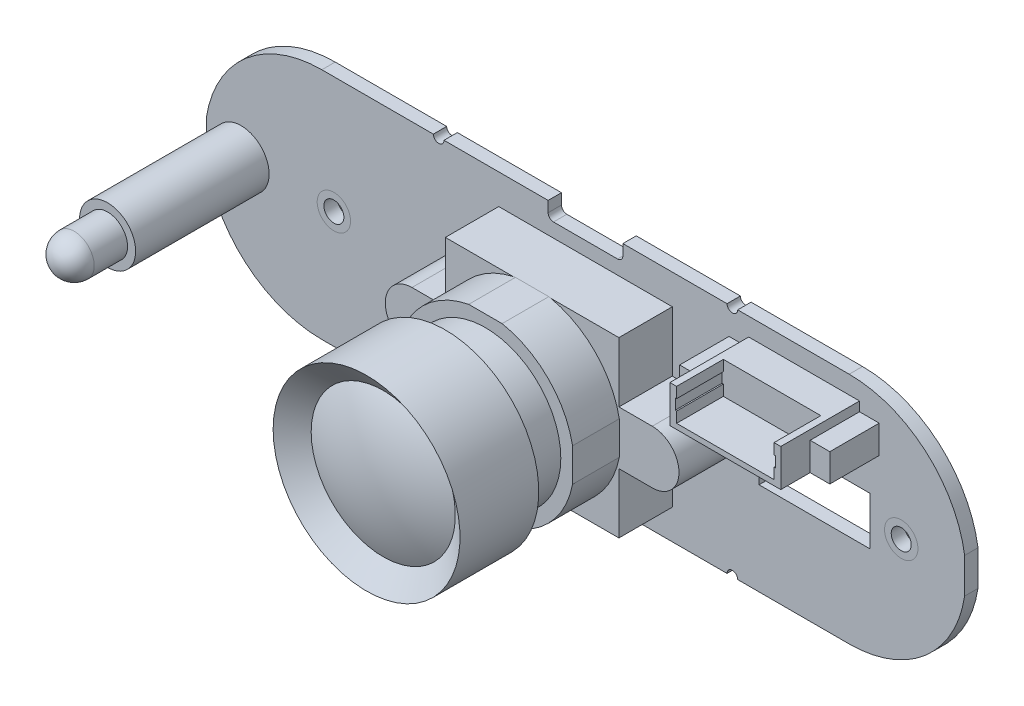
SolidWorks part; units mm, degrees
ref_plane "Front Plane" through (0, 0, 0) normal (0, 0, 1) x (1, 0, 0)
ref_plane "Top Plane" through (0, 0, 0) normal (0, 1, 0) x (1, 0, 0)
ref_plane "Right Plane" through (0, 0, 0) normal (1, 0, 0) x (0, 0, -1)
sketch "Sketch1" plane through (0, 0, 0) normal (0, 0, 1) x (1, 0, 0)
  line L0 (-19.75, 0) -> (19.75, 0) construction
  line L1 (-19.75, 8.75) -> (19.75, 8.75)
  line L2 (-19.75, -8.75) -> (19.75, -8.75)
  line L3 (28.4, 0) -> (-28.4, 0) construction
  line L4 (0, 8.75) -> (0, -8.75) construction
  arc A0 (-19.75, 8.75) -> (-19.75, -8.75) centre (-19.75, 0) ccw
  arc A1 (19.75, -8.75) -> (19.75, 8.75) centre (19.75, 0) ccw
  point P2 (0, 0)
  point P11 (0, 0)
  point P14 (0, 0)
  point P17 (28.4, 0)
  dimension "D1" = 8.75
  dimension "D2" = 39.5
  dimension "D3" = 56.8
extrude "Boss-Extrude1" add sketch "Sketch1" along normal mid plane 1
sketch "Sketch2" plane through (0, 0, 0) normal (0, 0, 1) x (1, 0, 0)
  line L0 (28.4, 0) -> (-28.4, 0) construction
  line L1 (28.4, 5) -> (28.4, -5)
  line L2 (-28.4, 5) -> (-28.4, -5)
  line L4 (28.4, 5) -> (30.4, 5)
  line L5 (30.4, 5) -> (30.4, -5)
  line L6 (30.4, -5) -> (28.4, -5)
  line L7 (-28.4, 5) -> (-30.4, 5)
  line L8 (-30.4, 5) -> (-30.4, -5)
  line L9 (-30.4, -5) -> (-28.4, -5)
  line L10 (19.75, 8.75) -> (-19.75, 8.75) construction
  line L11 (2.4, 7.55) -> (-2.4, 7.55)
  line L12 (2.8, 7.95) -> (2.8, 9.95)
  line L13 (2.8, 9.95) -> (-2.8, 9.95)
  line L14 (-2.8, 7.95) -> (-2.8, 9.95)
  line L15 (2.8, 7.55) -> (-2.8, 9.95) construction
  line L16 (2.8, 9.95) -> (-2.8, 7.55) construction
  arc A0 (2.4, 7.55) -> (2.8, 7.95) centre (2.4, 7.95) ccw
  arc A1 (-2.4, 7.55) -> (-2.8, 7.95) centre (-2.4, 7.95) cw
  point P0 (0, 8.75)
  point P4 (0, 0)
  point P8 (28.4, 0)
  point P11 (-28.4, 0)
  dimension "D6" = 0.4
  dimension "D1" = 56.8
  dimension "D2" = 2
  dimension "D3" = 10
  dimension "D4" = 5.6
  dimension "D5" = 2.4
extrude "Cut-Extrude1" cut sketch "Sketch2" against normal through all both and the other way through all
sketch "Sketch3" plane through (0, 0, 0) normal (0, 0, 1) x (1, 0, 0)
  line L0 (28.4, 0) -> (24.4, 0) construction
  line L1 (28.4, 1.3191) -> (28.4, -1.3191) construction
  line L2 (24.4, 0) -> (23.65, 0) construction
  line L3 (-28.4, 0) -> (-19.6, 0) construction
  line L4 (-28.4, -1.3191) -> (-28.4, 1.3191) construction
  line L5 (-19.6, 0) -> (-18.85, 0) construction
  line L6 (0, 0) -> (22.9, 0) construction
  line L8 (21.3, -1.8) -> (13, -1.8)
  line L9 (21.3, -1.8) -> (21.3, 1.8)
  line L10 (21.3, 1.8) -> (13, 1.8)
  line L11 (13, -1.8) -> (13, 1.8)
  line L12 (21.3, -1.8) -> (13, 1.8) construction
  line L13 (21.3, 1.8) -> (13, -1.8) construction
  circle A0 centre (23.65, 0) radius 0.75
  circle A1 centre (-18.85, 0) radius 0.75
  point P15 (17.15, 0)
  dimension "D1" = 1.5
  dimension "D3" = 1.5
  dimension "D2" = 4
  dimension "D4" = 42.5
  dimension "D5" = 7.1
  dimension "D6" = 8.3
  dimension "D7" = 3.6
extrude "Cut-Extrude2" cut sketch "Sketch3" against normal through all both and the other way through all
sketch "Sketch4" plane through (0, 0, 0.5) normal (0, 0, 1) x (1, 0, 0)
  line L3 (-28.4, -1.3191) -> (-28.4, 1.3191) construction
  circle A0 centre (-25.8, 0) radius 2.1
  dimension "D1" = 4.2
  dimension "D2" = 4.7
extrude "Boss-Extrude2" add sketch "Sketch4" along normal blind 10
sketch "Sketch5" plane through (0, 0, 10.5) normal (0, 0, 1) x (1, 0, 0)
  circle A0 centre (-25.8, 0) radius 1.5
  dimension "D1" = 3
extrude "Boss-Extrude3" add sketch "Sketch5" along normal blind 2.5
dome "Dome1" faces to dome 1 distance 1.5 reverse direction no elliptical dome no face at (-24.3, 0, 13) parameters "D1"=1.5
sketch "Sketch6" plane through (0, 0, 0.5) normal (0, 0, 1) x (1, 0, 0)
  line L0 (-9, 0) -> (9, 0) construction
  line L1 (6.5, 6.5) -> (-6.5, 6.5)
  line L2 (6.5, 6.5) -> (6.5, -6.5)
  line L3 (6.5, -6.5) -> (-6.5, -6.5)
  line L4 (-6.5, 6.5) -> (-6.5, -6.5)
  line L5 (6.5, 6.5) -> (-6.5, -6.5) construction
  line L6 (6.5, -6.5) -> (-6.5, 6.5) construction
  line L7 (-9, 2) -> (9, 2)
  line L8 (-9, -2) -> (9, -2)
  arc A0 (-9, 2) -> (-9, -2) centre (-9, 0) ccw
  arc A1 (9, -2) -> (9, 2) centre (9, 0) ccw
  point P0 (0, 0)
  point P8 (0, 0)
  dimension "D2" = 2
  dimension "D3" = 22
  dimension "D1" = 13
extrude "Boss-Extrude4" add sketch "Sketch6" along normal blind 4 contours L7 A0 L8 L4 | L4 L8 L2 L7 | L8 A1 L7 L2 | L8 L4 L3 L2 | L4 L7 L2 L1 region at (0, 4.25, 0.5) region at (8.5599, 0, 0.5) region at (0, 0, 0.5) region at (-8.5599, 0, 0.5) region at (0, -4.25, 0.5)
sketch "Sketch7" plane through (0, 0, 4.5) normal (0, 0, 1) x (1, 0, 0)
  line L0 (6.5315, 1.25) -> (6.5315, -1.25)
  line L1 (-1.25, 6.5315) -> (1.25, 6.5315)
  line L2 (-6.5315, -1.25) -> (-6.5315, 1.25)
  line L3 (1.25, -6.5315) -> (-1.25, -6.5315)
  arc A0 (1.25, -6.5315) -> (6.5315, -1.25) centre (0, 0) ccw
  arc A1 (6.5315, 1.25) -> (1.25, 6.5315) centre (0, 0) ccw
  arc A2 (-1.25, 6.5315) -> (-6.5315, 1.25) centre (0, 0) ccw
  arc A3 (-6.5315, -1.25) -> (-1.25, -6.5315) centre (0, 0) ccw
  point P14 (0, 0)
  dimension "D1" = 13.3
  dimension "D2" = 2.5
  dimension "D3" = 4
extrude "Boss-Extrude5" add sketch "Sketch7" along normal blind 3.5
sketch "Sketch8" plane through (0, 0, 8) normal (0, 0, 1) x (1, 0, 0)
  circle A0 centre (0, 0) radius 5.65
  dimension "D1" = 11.3
extrude "Boss-Extrude6" add sketch "Sketch8" along normal blind 3
sketch "Sketch9" plane through (0, 0, 0) normal (0, 1, 0) x (1, 0, 0)
  line L0 (0, -0.5) -> (0, -16.9) construction
  line L1 (-2.4, 0.5) -> (2.4, 0.5) construction
  line L2 (0, -11) -> (7, -11)
  line L3 (-5.65, -11) -> (5.65, -11) construction
  line L4 (7, -11) -> (7, -16.9)
  line L5 (7, -16.9) -> (5.4, -16.9) construction
  line L6 (5.4, -16.9) -> (5.4, -15.65) construction
  line L7 (7, -16.9) -> (5.4, -15.65)
  line L8 (0, -15.65) -> (5.4, -15.65) construction
  line L9 (0, -16.9) -> (0, -11)
  line L10 (-2.4, -0.5) -> (2.4, -0.5) construction
  arc A0 (5.4, -15.65) -> (0, -16.9) centre (0, -4.611) cw
  point P15 (0, -15.65)
  dimension "D5" = 12.289
  dimension "D1" = 16.4
  dimension "D2" = 7
  dimension "D3" = 1.6
  dimension "D4" = 1.25
revolve "Revolve1" add sketch "Sketch9" angle 360 about L0
sketch "Sketch10" plane through (0, 0, 0.5) normal (0, 0, 1) x (1, 0, 0)
  line L0 (10.75, 4.6) -> (22, 4.6)
  line L1 (22, 4.6) -> (22, 6.7)
  line L2 (22, 6.7) -> (20.525, 6.7)
  line L3 (20.525, 6.7) -> (20.525, 7.4)
  line L4 (20.525, 7.4) -> (12.225, 7.4)
  line L5 (12.225, 7.4) -> (12.225, 6.7)
  line L6 (12.225, 6.7) -> (10.75, 6.7)
  line L7 (10.75, 6.7) -> (10.75, 4.6)
  line L8 (19.75, 8.75) -> (2.8, 8.75) construction
  arc A2 (-9, 2) -> (-9, -2) centre (-9, 0) ccw construction
  dimension "D1" = 33
  dimension "D2" = 2.8
  dimension "D3" = 2.1
  dimension "D4" = 1.35
  dimension "D5" = 11.25
  dimension "D6" = 8.3
extrude "Boss-Extrude7" add sketch "Sketch10" along normal blind 3.7
sketch "Sketch11" plane through (0, 0, 4.2) normal (0, 0, 1) x (1, 0, 0)
  line L0 (10.75, 4.6) -> (22, 4.6) construction
  line L1 (12.225, 7.4) -> (20.525, 7.4)
  line L2 (12.225, 7.4) -> (12.225, 4.6)
  line L3 (12.225, 4.6) -> (20.525, 4.6)
  line L4 (20.525, 7.4) -> (20.525, 4.6)
  line L5 (12.225, 7.4) -> (20.525, 4.6) construction
  line L6 (12.225, 4.6) -> (20.525, 7.4) construction
  line L7 (20.525, 6.7) -> (20.525, 7.4) construction
  point P4 (16.375, 6)
extrude "Boss-Extrude8" add sketch "Sketch11" along normal blind 2.2
sketch "Sketch12" plane through (0, 0, 6.4) normal (0, 0, 1) x (1, 0, 0)
  line L16 (20.025, 7.4) -> (20.025, 6.6)
  line L17 (20.525, 7.4) -> (12.225, 7.4) construction
  line L18 (20.025, 6.6) -> (20.125, 6.6)
  line L19 (20.125, 6.6) -> (20.125, 5.8)
  line L20 (20.125, 5.8) -> (20.025, 5.8)
  line L21 (20.025, 5.8) -> (20.025, 5)
  line L22 (20.025, 5) -> (12.725, 5)
  line L23 (12.725, 5) -> (12.725, 5.8)
  line L24 (12.725, 5.8) -> (12.625, 5.8)
  line L25 (12.625, 5.8) -> (12.625, 6.6)
  line L26 (12.625, 6.6) -> (12.725, 6.6)
  line L27 (12.725, 6.6) -> (12.725, 7.4)
  line L28 (20.525, 7.4) -> (12.225, 7.4) construction
  line L29 (12.225, 4.6) -> (20.525, 4.6) construction
  line L30 (20.525, 4.6) -> (20.525, 7.4) construction
  line L31 (20.525, 4.6) -> (20.525, 6.7) construction
  line L32 (12.225, 7.4) -> (12.225, 6.7) construction
  line L33 (12.225, 7.4) -> (12.225, 4.6) construction
  line L34 (20.025, 7.4) -> (12.725, 7.4)
  dimension "D1" = 0.4
  dimension "D2" = 0.5
  dimension "D3" = 0.4
  dimension "D4" = 0.5
  dimension "D5" = 0.4
extrude "Cut-Extrude3" cut sketch "Sketch12" against normal blind 3.5
sketch "Sketch13" plane through (0, 0, 0.5) normal (0, 0, 1) x (1, 0, 0)
  circle A0 centre (-18.85, 0) radius 1.25
  circle A1 centre (23.65, 0) radius 1.25
  circle A2 centre (-18.85, 0) radius 0.75
  circle A3 centre (23.65, 0) radius 0.75
  dimension "D1" = 1.5
  dimension "D2" = 2.5
split line "Split Line1"
sketch "Sketch14" plane through (0, 0, -0.5) normal (0, 0, -1) x (-1, 0, 0)
  circle A0 centre (-23.65, 0) radius 1.25
  circle A1 centre (18.85, 0) radius 1.25
  dimension "D1" = 2.5
split line "Split Line2"
sketch "Sketch15" plane through (0, 0, 0.5) normal (0, 0, 1) x (1, 0, 0)
  line L0 (-28.4, 0) -> (28.4, 0) construction
  line L1 (28.4, 1.3191) -> (28.4, -1.3191) construction
  line L2 (0, 0) -> (0, -8.75) construction
  line L3 (-19.75, -8.75) -> (19.75, -8.75) construction
  line L4 (19.75, 8.75) -> (2.8, 8.75) construction
  circle A0 centre (11, 8.75) radius 0.4
  circle A1 centre (-11, 8.75) radius 0.4
  circle A2 centre (-11, -8.75) radius 0.4
  circle A3 centre (11, -8.75) radius 0.4
  point P6 (0, 0)
  dimension "D1" = 0.8
  dimension "D2" = 22
extrude "Cut-Extrude4" cut sketch "Sketch15" against normal up to next
